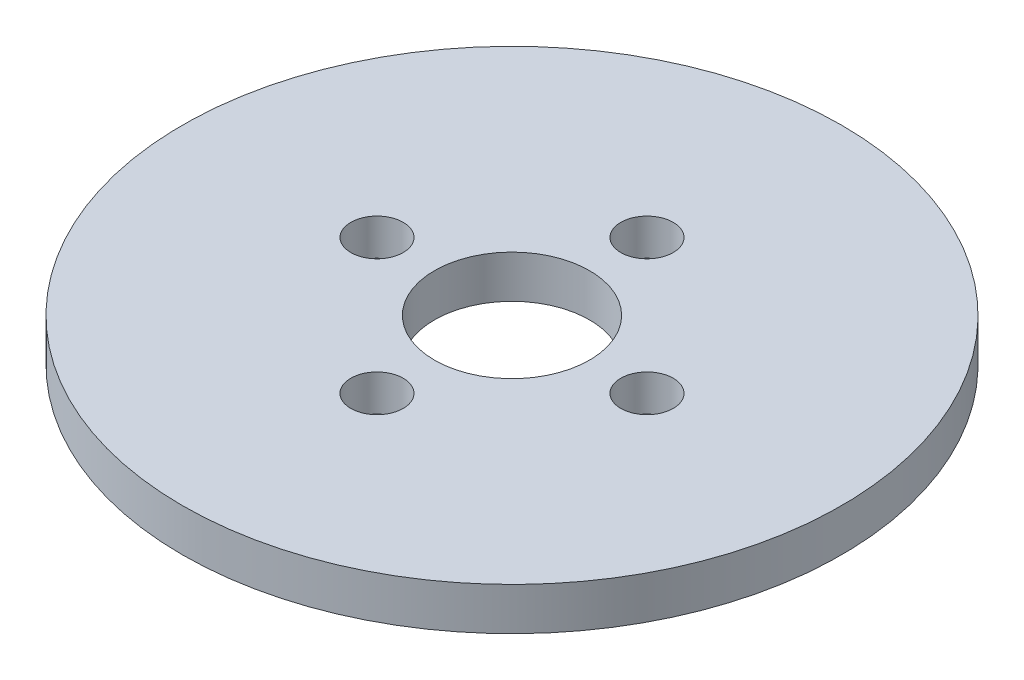
SolidWorks part; units mm, degrees
ref_plane "Front Plane" through (0, 0, 0) normal (0, 0, 1) x (1, 0, 0)
ref_plane "Top Plane" through (0, 0, 0) normal (0, 1, 0) x (1, 0, 0)
ref_plane "Right Plane" through (0, 0, 0) normal (1, 0, 0) x (0, 0, -1)
sketch "Sketch1" plane through (0, 0, 0) normal (0, 1, 0) x (1, 0, 0)
  circle A0 centre (0, 0) radius 85
  dimension "FLANGE_OD" = 170
extrude "Boss-Extrude1" add sketch "Sketch1" along normal blind 11
sketch "Sketch2" plane through (0, 0, 0) normal (0, 1, 0) x (1, 0, 0)
  circle A0 centre (0, 0) radius 20
  dimension "BORE_D" = 40
extrude "Cut-Extrude1" cut sketch "Sketch2" along normal through all
sketch "Sketch3" plane through (0, 11, 0) normal (0, 1, 0) x (1, 0, 0)
  circle A0 centre (0, 0) radius 34.8189 construction
  circle A1 centre (-34.8189, 0) radius 6.758
  dimension "BOLT_D" = 13.516
  dimension "BOLT_PCD" = 69.6378
extrude "Cut-Extrude2" cut sketch "Sketch3" against normal blind 9.4145
pattern_circular "CirPattern1" count 4 over 360 about axis through (0, 0, 0) along (0, 1, 0) of "Cut-Extrude2"
